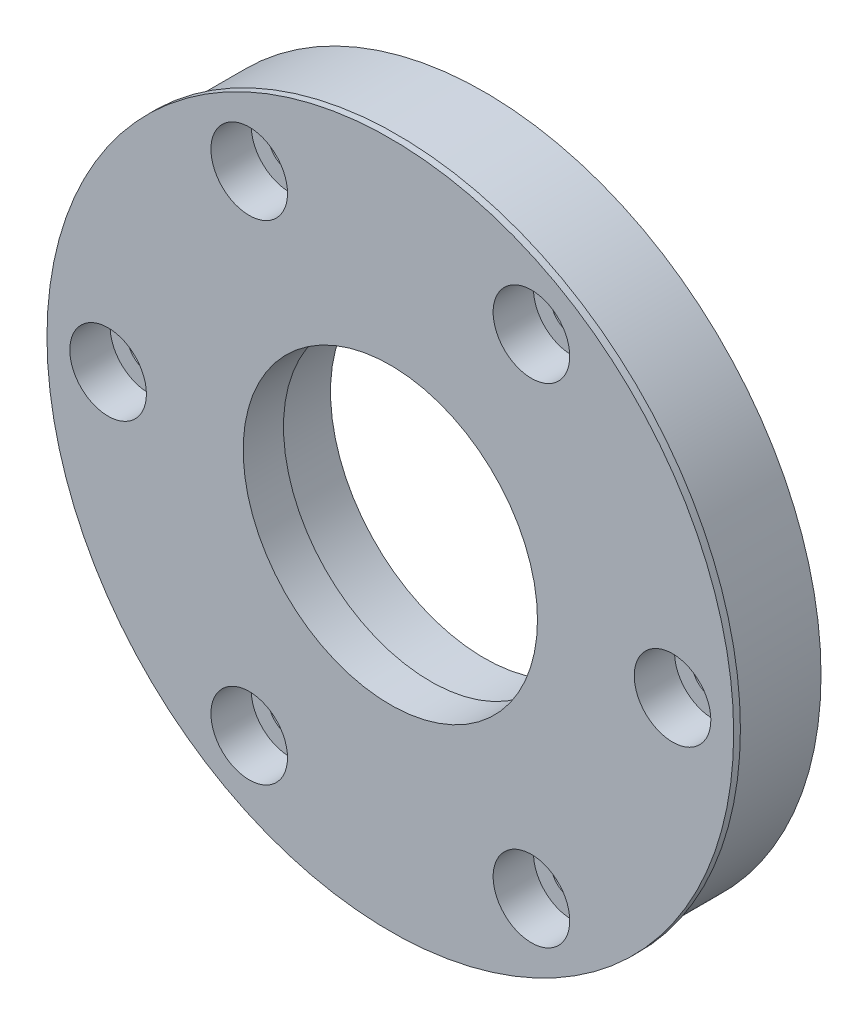
SolidWorks part; units mm, degrees
material "ABS"
ref_plane "Front Plane" through (0, 0, 0) normal (0, 0, 1) x (1, 0, 0)
ref_plane "Top Plane" through (0, 0, 0) normal (0, 1, 0) x (1, 0, 0)
ref_plane "Right Plane" through (0, 0, 0) normal (1, 0, 0) x (0, 0, -1)
sketch "Output Master Sketch" plane through (0, 0, 0) normal (0, 0, 1) x (1, 0, 0)
  circle A0 centre (0, 0) radius 21 construction
  circle A1 centre (21, 0) radius 2.85 construction
  circle A2 centre (10.5, -18.1865) radius 2.85 construction
  circle A3 centre (-10.5, -18.1865) radius 2.85 construction
  circle A4 centre (-21, 0) radius 2.85 construction
  circle A5 centre (-10.5, 18.1865) radius 2.85 construction
  circle A6 centre (10.5, 18.1865) radius 2.85 construction
  circle A7 centre (0, 0) radius 25.05
  point P17 (0, 0)
sketch "Sketch2" plane through (0, 0, 0) normal (0, 0, 1) x (1, 0, 0)
  circle A0 centre (0, 0) radius 25.05
  circle A1 centre (0, 0) radius 25.05 construction
extrude "Boss-Extrude1" add sketch "Sketch2" along normal blind 7
sketch "Sketch3" plane through (0, 0, 7) normal (0, 0, 1) x (1, 0, 0)
  circle A0 centre (-21, 0) radius 2.85
  circle A1 centre (-21, 0) radius 2.85 construction
  circle A2 centre (-10.5, 18.1865) radius 2.85
  circle A3 centre (10.5, 18.1865) radius 2.85
  circle A4 centre (21, 0) radius 2.85
  circle A5 centre (10.5, -18.1865) radius 2.85
  circle A6 centre (-10.5, -18.1865) radius 2.85
  point P18 (0, 0)
  dimension "D1" = 5.7
  dimension "D2" = 6
extrude "Dowel Pin Cutout" cut sketch "Sketch3" against normal blind 3
sketch "Sketch4" plane through (0, 0, 7) normal (0, 0, 1) x (1, 0, 0)
  circle A0 centre (0, 0) radius 25.05
  circle A1 centre (0, 0) radius 25.55
  circle A3 centre (0, 0) radius 25.05 construction
  dimension "D1" = 0.5
extrude "Main Housing Bearing Retainer" add sketch "Sketch4" against normal blind 0.5
sketch "Sketch5" plane through (0, 0, 0) normal (0, 0, -1) x (-1, 0, 0)
  circle A0 centre (-21, 0) radius 1.55
  circle A1 centre (-10.5, 18.1865) radius 1.55
  circle A2 centre (10.5, 18.1865) radius 1.55
  circle A3 centre (21, 0) radius 1.55
  circle A4 centre (10.5, -18.1865) radius 1.55
  circle A5 centre (-10.5, -18.1865) radius 1.55
  point P15 (0, 0)
  dimension "D1" = 3.1
  dimension "D2" = 6
extrude "M3 Thru" cut sketch "Sketch5" against normal through all
sketch "Sketch6" plane through (0, 0, 0) normal (0, 0, -1) x (-1, 0, 0)
  circle A0 centre (-21, 0) radius 3
  circle A1 centre (-10.5, 18.1865) radius 3
  circle A2 centre (10.5, 18.1865) radius 3
  circle A3 centre (21, 0) radius 3
  circle A4 centre (10.5, -18.1865) radius 3
  circle A5 centre (-10.5, -18.1865) radius 3
  point P15 (0, 0)
  dimension "D1" = 6
  dimension "D2" = 6
extrude "M3 Button Head Cutout" cut sketch "Sketch6" against normal blind 1.7
sketch "Sketch8" plane through (0, 0, 7) normal (0, 0, 1) x (1, 0, 0)
  circle A0 centre (0, 0) radius 11.45
  dimension "D1" = 22.9
extrude "Input Shaft Bearing Cutout" cut sketch "Sketch8" against normal through all
sketch "Sketch9" plane through (0, 0, 0) normal (0, 0, -1) x (-1, 0, 0)
  circle A0 centre (0, 0) radius 11.45
  circle A1 centre (0, 0) radius 10.95
  circle A2 centre (0, 0) radius 11.45 construction
  dimension "D1" = 0.5
extrude "Input Shaft Bearing Retainer" add sketch "Sketch9" along normal blind 3 from surface starting at face at (11.45, 0, 7)
